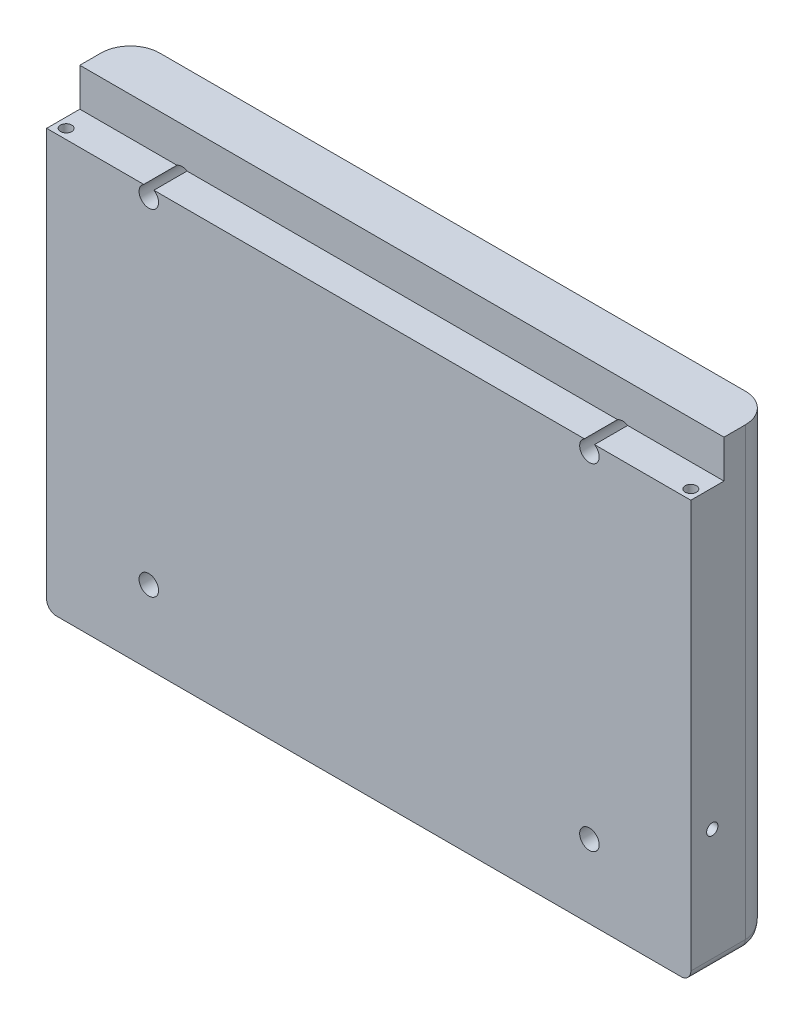
SolidWorks part; units mm, degrees
material "PLA"
ref_plane "Front Plane" through (0, 0, 0) normal (0, 0, 1) x (1, 0, 0)
ref_plane "Top Plane" through (0, 0, 0) normal (0, 1, 0) x (1, 0, 0)
ref_plane "Right Plane" through (0, 0, 0) normal (1, 0, 0) x (0, 0, -1)
sketch "Sketch1" plane through (0, 0, 0) normal (0, 0, 1) x (1, 0, 0)
  line L0 (0, 0) -> (0, -138.8145) construction
  line L1 (-82.55, -80.8019) -> (82.55, -80.8019)
  line L2 (-82.55, -80.8019) -> (-82.55, 9.1981)
  line L3 (-82.55, 9.1981) -> (82.55, 9.1981)
  line L4 (82.55, -80.8019) -> (82.55, 9.1981)
  point P7 (0, -80.8019)
  dimension "D1" = 165.1
  dimension "D2" = 90
extrude "Boss-Extrude1" add sketch "Sketch1" along normal blind 5
sketch "Sketch2" plane through (0, 9.1981, 0) normal (0, 1, 0) x (1, 0, 0)
  line L0 (-82.55, -5) -> (-82.55, 0) construction
  line L1 (82.55, -5) -> (82.55, 0) construction
  circle A0 centre (-80.05, -2.5) radius 1.45
  circle A1 centre (80.05, -2.5) radius 1.45
  point P7 (-82.55, -2.5)
  dimension "D2" = 2.9
  dimension "D4" = 2.9
  dimension "D1" = 2.5
  dimension "D3" = 2.5
extrude "Cut-Extrude1" cut sketch "Sketch2" against normal blind 7 contours A1 | A0
sketch "Sketch4" plane through (0, 0, 0) normal (0, 0, -1) x (-1, 0, 0)
  line L4 (-82.55, 9.1981) -> (-82.55, -80.8019)
  line L5 (-82.55, -80.8019) -> (82.55, -80.8019)
  line L6 (82.55, -80.8019) -> (82.55, 9.1981)
  line L7 (82.55, 9.1981) -> (-82.55, 9.1981)
  line L8 (-82.55, 9.1981) -> (-82.55, -80.8019)
  line L9 (-82.55, -80.8019) -> (82.55, -80.8019)
  line L10 (82.55, -80.8019) -> (82.55, 9.1981)
  line L11 (82.55, 9.1981) -> (-82.55, 9.1981)
  dimension "D1" = 0
extrude "Boss-Extrude2" add sketch "Sketch4" along normal blind 3.5
ref_plane "Plane1" through (-27.79, 0, 0) normal (-1, 0, 0) x (0, 0, 1)
sketch "Sketch8" plane through (82.55, 0, 0) normal (1, 0, 0) x (0, 0, -1)
  line L2 (0.5, -68.0019) -> (0.5, -65.1019) construction
  circle A2 centre (0.5, -66.5519) radius 1.45
extrude "Cut-Extrude5" cut sketch "Sketch8" against normal blind 3
mirror "Mirror2" about plane through (0, 0, 0) normal (1, 0, 0) of "Cut-Extrude5"
sketch "Sketch10" plane through (0, -80.8019, 0) normal (0, -1, 0) x (1, 0, 0)
  line L4 (-82.55, 5) -> (-82.55, -3.5)
  line L5 (-82.55, -3.5) -> (82.55, -3.5)
  line L6 (82.55, -3.5) -> (82.55, 5)
  line L7 (82.55, 5) -> (-82.55, 5)
  line L8 (-82.55, 5) -> (-82.55, -3.5)
  line L9 (-82.55, -3.5) -> (82.55, -3.5)
  line L10 (82.55, -3.5) -> (82.55, 5)
  line L11 (82.55, 5) -> (-82.55, 5)
  dimension "D1" = 0
extrude "Boss-Extrude4" add sketch "Sketch10" along normal blind 17
fillet "Fillet1" radius 2.5 2 edges at (82.55, -97.8019, 0.75) (-82.55, -97.8019, 0.75)
sketch "Sketch11" plane through (0, 0, -3.5) normal (0, 0, -1) x (-1, 0, 0)
  line L0 (0, 9.1981) -> (0, -97.8019) construction
  line L1 (82.55, 9.1981) -> (-82.55, 9.1981) construction
  line L2 (80.05, -97.8019) -> (-80.05, -97.8019) construction
  line L3 (-82.55, -43.0519) -> (82.55, -43.0519) construction
  line L4 (-82.55, 9.1981) -> (-82.55, -95.3019) construction
  line L5 (82.55, -95.3019) -> (82.55, 9.1981) construction
  line L7 (-51.7, 2.3981) -> (51.7, 2.3981)
  line L8 (-51.7, 2.3981) -> (-51.7, -88.5019)
  line L9 (-51.7, -88.5019) -> (51.7, -88.5019)
  line L10 (51.7, 2.3981) -> (51.7, -88.5019)
  point P16 (0, 2.3981)
  point P17 (-51.7, -43.0519)
  dimension "D1" = 103.4
  dimension "D2" = 90.9
extrude "Cut-Extrude6" cut sketch "Sketch11" against normal blind 6
sketch "Sketch12" plane through (0, 0, -3.5) normal (0, 0, -1) x (-1, 0, 0)
  line L0 (82.55, -95.3019) -> (82.55, 9.1981) construction
  line L1 (-82.55, 9.1981) -> (82.55, 9.1981)
  line L2 (-82.55, 9.1981) -> (-82.55, 2.3981)
  line L3 (-82.55, 2.3981) -> (82.55, 2.3981)
  line L4 (82.55, 9.1981) -> (82.55, 2.3981)
  line L5 (51.7, 2.3981) -> (-51.7, 2.3981) construction
  dimension "D1" = 0
extrude "Boss-Extrude5" add sketch "Sketch12" along normal blind 12.95
sketch "Sketch13" plane through (0, 9.1981, 0) normal (0, 1, 0) x (1, 0, 0)
  line L0 (82.55, -5) -> (82.55, 16.45) construction
  line L1 (-82.55, 16.45) -> (82.55, 16.45)
  line L2 (-82.55, 16.45) -> (-82.55, 3.5)
  line L3 (-82.55, 3.5) -> (82.55, 3.5)
  line L4 (82.55, 16.45) -> (82.55, 3.5)
  dimension "D1" = 12.95
extrude "Boss-Extrude6" add sketch "Sketch13" along normal blind 9.75
sketch "Sketch14" plane through (0, 0, -3.5) normal (0, 0, -1) x (-1, 0, 0)
  line L0 (-51.7, -88.5019) -> (-51.7, -97.8019)
  line L1 (51.7, -88.5019) -> (51.7, -97.8019)
  line L2 (51.7, -97.8019) -> (80.05, -97.8019)
  line L8 (-51.7, 2.3981) -> (-82.55, 2.3981)
  line L9 (-82.55, 2.3981) -> (-82.55, -95.3019)
  line L10 (-80.05, -97.8019) -> (80.05, -97.8019)
  line L11 (82.55, -95.3019) -> (82.55, 2.3981)
  line L12 (82.55, 2.3981) -> (51.7, 2.3981)
  line L13 (51.7, 2.3981) -> (51.7, -88.5019)
  line L14 (51.7, -88.5019) -> (-51.7, -88.5019)
  line L15 (-51.7, -88.5019) -> (-51.7, 2.3981)
  line L16 (-51.7, 2.3981) -> (-82.55, 2.3981)
  line L17 (-82.55, 2.3981) -> (-82.55, -95.3019)
  line L18 (-80.05, -97.8019) -> (-51.7, -97.8019)
  line L19 (82.55, -95.3019) -> (82.55, 2.3981)
  line L20 (82.55, 2.3981) -> (51.7, 2.3981)
  line L21 (51.7, 2.3981) -> (51.7, -88.5019)
  line L23 (-51.7, -88.5019) -> (-51.7, 2.3981)
  arc A2 (-82.55, -95.3019) -> (-80.05, -97.8019) centre (-80.05, -95.3019) ccw
  arc A3 (80.05, -97.8019) -> (82.55, -95.3019) centre (80.05, -95.3019) ccw
  arc A4 (-82.55, -95.3019) -> (-80.05, -97.8019) centre (-80.05, -95.3019) ccw
  arc A5 (80.05, -97.8019) -> (82.55, -95.3019) centre (80.05, -95.3019) ccw
  dimension "D1" = 0
extrude "Boss-Extrude7" add sketch "Sketch14" along normal up to surface (12.95 mm away) up to face at (0, 10.6731, -16.45)
fillet "Fillet2" radius 7.5 6 edges at (65.875, -97.8019, -16.45) (81.8178, -97.0697, -16.45) (-65.875, -97.8019, -16.45) (-81.8178, -97.0697, -16.45) (82.55, -38.1769, -16.45) (-82.55, -38.1769, -16.45)
sketch "Sketch15" plane through (0, 0, -16.45) normal (0, 0, -1) x (-1, 0, 0)
  circle A0 centre (56.3625, -79.0219) radius 1.35 construction
  circle A1 centre (56.3625, 7.0606) radius 1.35 construction
  circle A2 centre (-56.5625, 7.0606) radius 1.35 construction
  circle A3 centre (-56.5625, -79.0219) radius 1.35 construction
  circle A4 centre (56.3625, -79.0219) radius 1.35
  circle A5 centre (56.3625, 7.0606) radius 1.35
  circle A6 centre (-56.5625, 7.0606) radius 1.35
  circle A7 centre (-56.5625, -79.0219) radius 1.35
extrude "Cut-Extrude7" cut sketch "Sketch15" against normal blind 8.65
sketch "Sketch16" plane through (0, 0, -7.8) normal (0, 0, -1) x (-1, 0, 0)
  circle A0 centre (56.3625, 7.0606) radius 2.5
  circle A1 centre (-56.5625, 7.0606) radius 2.5
  circle A2 centre (-56.5625, -79.0219) radius 2.5
  circle A3 centre (56.3625, -79.0219) radius 2.5
  dimension "D1" = 5
  dimension "D2" = 5
extrude "Cut-Extrude8" cut sketch "Sketch16" against normal through all
